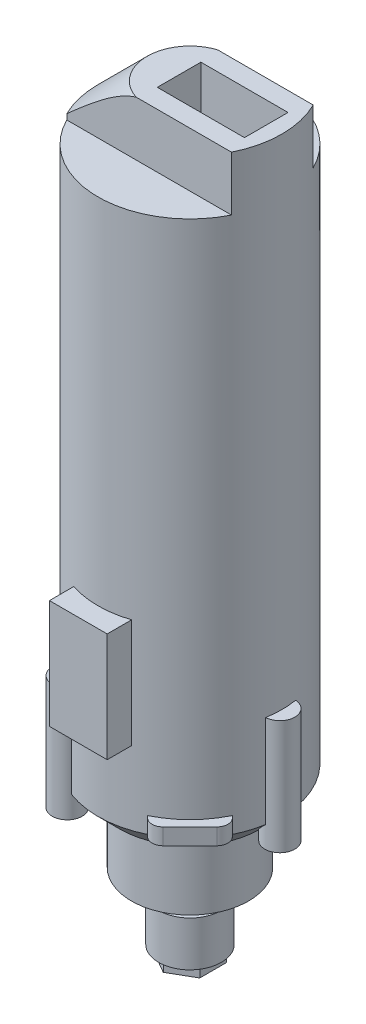
SolidWorks part; units mm, degrees
material "1060 Legierung"
ref_plane "Ebene vorne" through (0, 0, 0) normal (0, 0, 1) x (1, 0, 0)
ref_plane "Ebene oben" through (0, 0, 0) normal (0, 1, 0) x (1, 0, 0)
ref_plane "Ebene rechts" through (0, 0, 0) normal (1, 0, 0) x (0, 0, -1)
sketch "Skizze1" plane through (0, 0, 0) normal (0, 0, 1) x (1, 0, 0)
  line L0 (0, 0) -> (0, 250.353) construction
  line L1 (8.5, 0) -> (21.5, 0)
  line L2 (21.5, 0) -> (21.5, 25)
  line L3 (21.5, 25) -> (25.75, 25)
  line L4 (25.75, 25) -> (33.75, 33)
  line L5 (33.75, 33) -> (33.75, 230)
  line L6 (33.75, 230) -> (0, 230)
  line L7 (0, 230) -> (0, -28.5)
  line L8 (0, -28.5) -> (11.5, -28.5)
  line L9 (11.5, -28.5) -> (11.5, -8)
  line L10 (11.5, -8) -> (8.5, -8)
  line L11 (8.5, -8) -> (8.5, 0)
  dimension "D1" = 43
  dimension "D2" = 17
  dimension "D3" = 23
  dimension "D4" = 67.5
  dimension "D5" = 230
  dimension "D6" = 25
  dimension "D7" = 45
  dimension "D8" = 8
  dimension "D9" = 28.5
  dimension "D10" = 20.5
revolve "Rotation1" add sketch "Skizze1" angle 360 about L0
sketch "Skizze2" plane through (0, 0, 0) normal (0, 0, 1) x (1, 0, 0)
  line L0 (0, 0) -> (0, 143.6204) construction
  line L1 (-10.6007, 60) -> (10.6007, 60)
  line L2 (-10.6007, 60) -> (-10.6007, 100)
  line L3 (-10.6007, 100) -> (10.6007, 100)
  line L4 (10.6007, 60) -> (10.6007, 100)
  dimension "D1" = 21.2013
  dimension "D2" = 40
  dimension "D3" = 60
extrude "Aufsatz-Linear austragen1" add sketch "Skizze2" along normal blind 41
sketch "Skizze3" plane through (0, 25, 0) normal (0, -1, 0) x (1, 0, 0)
  line L0 (0, 0) -> (42.6448, 0) construction
  line L1 (0, 0) -> (-21.3519, 36.9825) construction
  line L2 (0, 0) -> (-20.463, -35.443) construction
  circle A0 centre (0, 0) radius 33 construction
  circle A1 centre (33, 0) radius 5.5
  circle A2 centre (-16.5, 28.5788) radius 5.5
  circle A3 centre (-16.5, -28.5788) radius 5.5
  dimension "D1" = 11
  dimension "D2" = 66
  dimension "D3" = 120
  dimension "D4" = 120
extrude "Aufsatz-Linear austragen2" add sketch "Skizze3" against normal blind 42
sketch "Skizze4" plane through (0, -28.5, 0) normal (0, -1, 0) x (1, 0, 0)
  circle A0 centre (0, 0) radius 4
  dimension "D1" = 8
extrude "Schnitt-Linear austragen1" cut sketch "Skizze4" against normal blind 25
sketch "Skizze5" plane through (0, -28.5, 0) normal (0, -1, 0) x (1, 0, 0)
  line L1 (-8.5, -4.9075) -> (0, -9.815)
  line L2 (0, -9.815) -> (8.5, -4.9075)
  line L3 (8.5, -4.9075) -> (8.5, 4.9075)
  line L4 (8.5, 4.9075) -> (0, 9.815)
  line L5 (0, 9.815) -> (-8.5, 4.9075)
  line L6 (-8.5, 4.9075) -> (-8.5, -4.9075)
  circle A0 centre (0, 0) radius 8.5 construction
  dimension "D1" = 17
extrude "Schnitt-Linear austragen2" cut sketch "Skizze5" against normal blind 4 flip side to cut
ref_axis "Achse1" through (0, -41.425, 0) along (0, 1, 0)
ref_plane "Ebene1" through (0, 0, 0) normal (0.7071, 0, 0.7071) x (0, 1, 0)
sketch "Skizze6" plane through (0, 0, 0) normal (0.7071, 0, 0.7071) x (0, 1, 0)
  line L0 (0, 0) -> (249.4244, 0) construction
  line L2 (33, -11) -> (39, -11)
  line L3 (33, -11) -> (33, 11)
  line L4 (33, 11) -> (39, 11)
  line L5 (39, -11) -> (39, 11)
  line L6 (33, -11) -> (39, 11) construction
  line L7 (33, 11) -> (39, -11) construction
  point P3 (36, 0)
  dimension "D1" = 33
  dimension "D2" = 6
  dimension "D3" = 22
extrude "Aufsatz-Linear austragen3" add sketch "Skizze6" along normal blind 37
fillet "Verrundung1" radius 4 2 edges at (18.3848, 36, 33.9411) (33.9411, 36, 18.3848)
sketch "Skizze7" plane through (0, 230, 0) normal (0, 1, 0) x (1, 0, 0)
  line L0 (-38.632, 0) -> (52.4156, 0) construction
  line L1 (-30.2335, 15) -> (30.2335, 15)
  line L2 (-30.2335, -15) -> (30.2335, -15)
  circle A0 centre (0, 0) radius 33.75 construction
  arc A1 (-30.2335, 15) -> (-30.2335, -15) centre (0, 0) ccw
  arc A2 (30.2335, -15) -> (30.2335, 15) centre (0, 0) ccw
  dimension "D1" = 30
extrude "Aufsatz-Linear austragen4" add sketch "Skizze7" along normal blind 20
sketch "Skizze8" plane through (0, 250, 0) normal (0, 1, 0) x (1, 0, 0)
  line L0 (0, 0) -> (51.694, 0) construction
  line L2 (-4, -8) -> (28, -8)
  line L3 (-4, -8) -> (-4, 8)
  line L4 (-4, 8) -> (28, 8)
  line L5 (28, -8) -> (28, 8)
  line L6 (-4, -8) -> (28, 8) construction
  line L7 (-4, 8) -> (28, -8) construction
  point P3 (12, 0)
  dimension "D1" = 16
  dimension "D2" = 32
  dimension "D3" = 12
extrude "Schnitt-Linear austragen3" cut sketch "Skizze8" against normal blind 30
chamfer "Fase1" distance 18 angle 45 1 edges at (-33.75, 250, 0)
